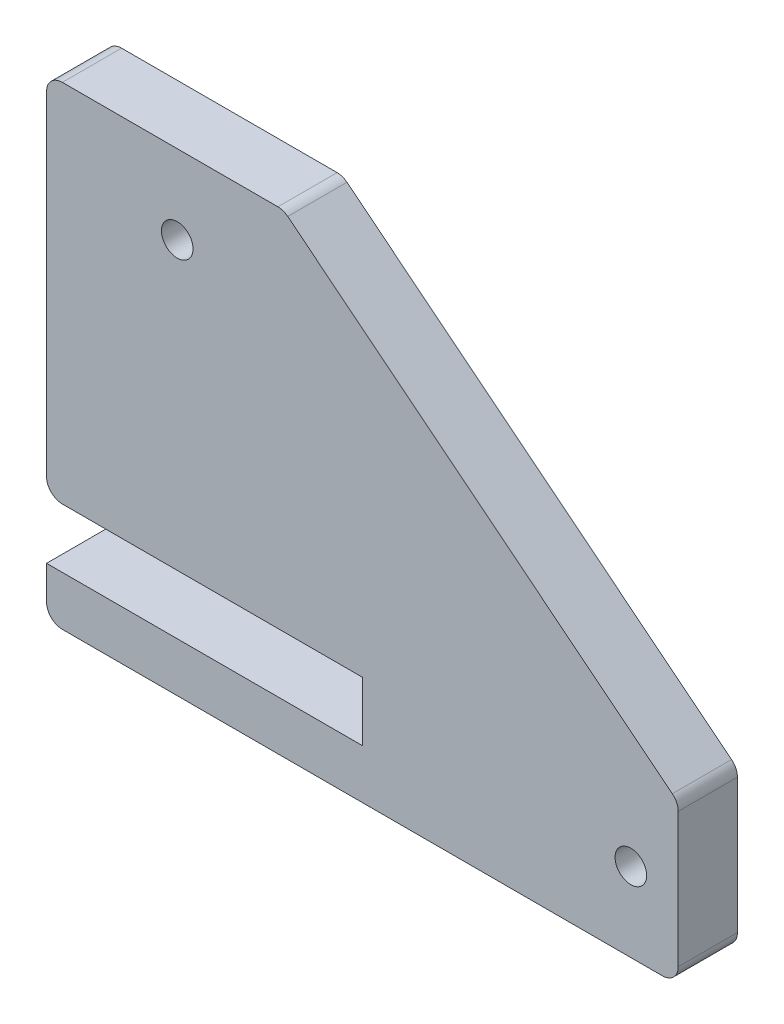
SolidWorks part; units mm, degrees
ref_plane "Front Plane" through (0, 0, 0) normal (0, 0, 1) x (1, 0, 0)
ref_plane "Top Plane" through (0, 0, 0) normal (0, 1, 0) x (1, 0, 0)
ref_plane "Right Plane" through (0, 0, 0) normal (1, 0, 0) x (0, 0, -1)
sketch "Sketch1" plane through (0, 0, 0) normal (0, 0, 1) x (1, 0, 0)
  line L0 (-25.4, 2.3813) -> (-25.4, 6.35)
  line L1 (-25.4, -2.3813) -> (0, -2.3813)
  line L3 (-25.4, 2.3813) -> (0, 2.3813)
  line L4 (0, -2.3813) -> (0, 2.3813)
  line L5 (-25.4, 6.35) -> (25.4, 6.35)
  line L6 (0, 0) -> (25.4, 0) construction
  line L7 (25.4, 6.35) -> (25.4, -6.35)
  line L8 (-25.4, -6.35) -> (25.4, -6.35)
  line L9 (-25.4, -2.3813) -> (-25.4, -6.35)
  line L11 (-25.4, 6.35) -> (25.4, 6.35)
  line L12 (-25.4, 6.35) -> (-25.4, 31.75)
  line L13 (-25.4, 31.75) -> (25.4, 31.75)
  line L14 (25.4, 6.35) -> (25.4, 31.75)
  dimension "D1" = 25.4
  dimension "D2" = 4.7625
  dimension "D3" = 25.4
  dimension "D4" = 12.7
  dimension "D5" = 38.1
extrude "Boss-Extrude1" add sketch "Sketch1" along normal mid plane 4.7625 contours L5 L14 L13 L12 | L6 L4 L1 L9 L8 L7 | L4 L6 L7 L5 L0 L3 region at (2.9308, 3.6329, 0) region at (0, 19.05, 0) region at (2.9308, -3.6329, 0)
sketch "Sketch2" plane through (0, 0, 2.3813) normal (0, 0, 1) x (1, 0, 0)
  line L0 (0, 0) -> (25.4, 0) construction
  line L2 (25.4, -6.35) -> (25.4, 31.75) construction
  circle A0 centre (21.59, 0) radius 1.27
  point P3 (0, 0)
  point P4 (25.4, 0)
  point P7 (0, 0)
  point P10 (0, 0)
  point P11 (0, 0)
  dimension "D1" = 2.54
  dimension "D2" = 2.54
extrude "Cut-Extrude1" cut sketch "Sketch2" against normal through all
sketch "Sketch3" plane through (0, 0, 2.3813) normal (0, 0, 1) x (1, 0, 0)
  circle A0 centre (-14.888, 25.4) radius 1.27
  circle A1 centre (21.59, 0) radius 1.27 construction
  point P4 (0.4956, 14.1487)
  point P5 (0, 0)
  point P6 (1.7282, 15.8325)
  dimension "D1" = 44.45
  dimension "D2" = 25.4
extrude "Cut-Extrude2" cut sketch "Sketch3" against normal through all
sketch "Sketch4" plane through (0, 0, 2.3813) normal (0, 0, 1) x (1, 0, 0)
  line L0 (-6.35, 31.75) -> (25.4, 6.35)
  line L1 (-25.4, 31.75) -> (25.4, 31.75) construction
  line L2 (25.4, -6.35) -> (25.4, 31.75) construction
  line L3 (-6.35, 31.75) -> (25.4, 31.75)
  line L4 (25.4, 31.75) -> (25.4, 6.35)
  dimension "D1" = 25.4
  dimension "D2" = 31.75
extrude "Cut-Extrude3" cut sketch "Sketch4" against normal through all
fillet "Fillet1" radius 1.27 6 edges at (-25.4, -6.35, 0) (25.4, -6.35, 0) (-25.4, 2.3813, 0) (-25.4, 31.75, 0) (25.4, 6.35, 0) (-6.35, 31.75, 0)
equation "\"D2@Sketch1\"=\"thick@FullAssem.Assembly\""
equation "\"D1@Sketch2\"=\"rodThick@FullAssem.Assembly\""
equation "\"D1@Boss-Extrude1\"=\"thick@FullAssem.Assembly\""
